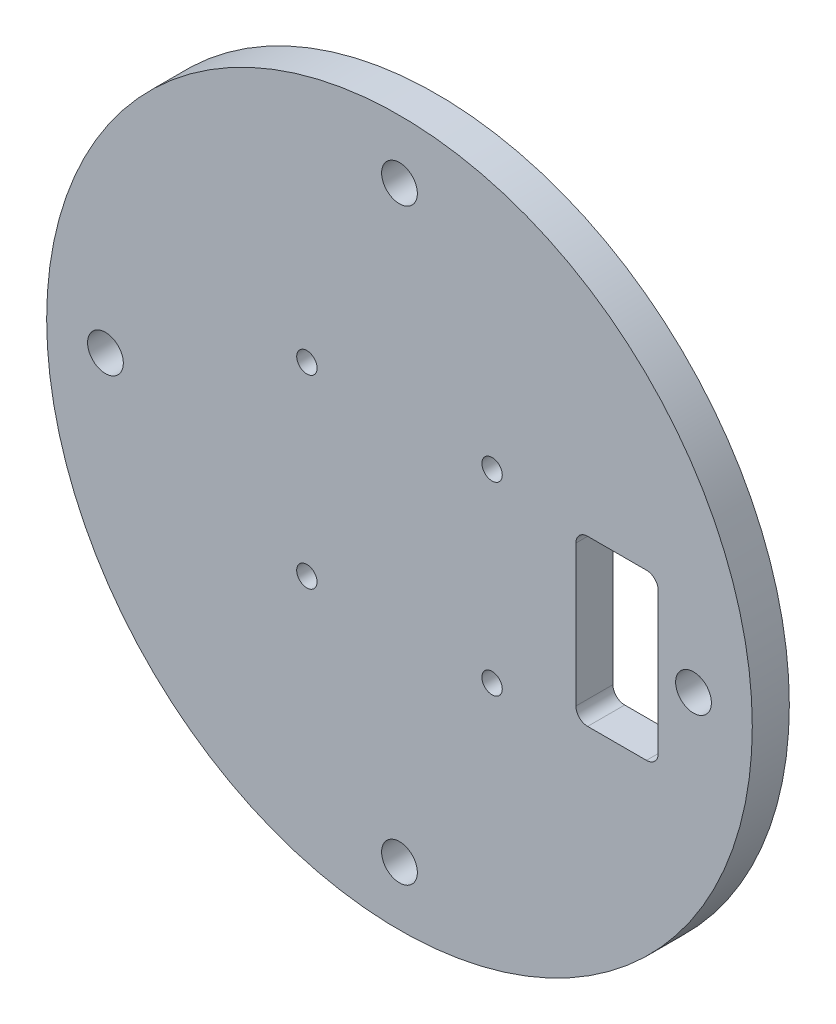
SolidWorks part; units mm, degrees
material "Hexcel AS4C (3000 Filaments)"
ref_plane "Front Plane" through (0, 0, 0) normal (0, 0, 1) x (1, 0, 0)
ref_plane "Top Plane" through (0, 0, 0) normal (0, 1, 0) x (1, 0, 0)
ref_plane "Right Plane" through (0, 0, 0) normal (1, 0, 0) x (0, 0, -1)
sketch "Sketch1" plane through (0, 0, 0) normal (0, 0, 1) x (1, 0, 0)
  circle A0 centre (0, 0) radius 38.1
  dimension "D1" = 76.2
extrude "Boss-Extrude1" add sketch "Sketch1" along normal blind 4 contours A0
sketch "Sketch2" plane through (0, 0, 4) normal (0, 0, 1) x (1, 0, 0)
  circle A0 centre (10, 10) radius 1.1
  circle A1 centre (10, -10) radius 1.1
  circle A2 centre (-10, -10) radius 1.1
  circle A3 centre (-10, 10) radius 1.1
  point P12 (0, 0)
  point P21 (0, 0)
  dimension "D3" = 2.2
  dimension "D1" = 10
  dimension "D2" = 10
  dimension "D4" = 4
extrude "Cut-Extrude1" cut sketch "Sketch2" against normal through all
sketch "Sketch3" plane through (0, 0, 4) normal (0, 0, 1) x (1, 0, 0)
  circle A0 centre (0, -31.75) radius 1.9304
  circle A1 centre (-31.75, 0) radius 1.9304
  circle A2 centre (0, 31.75) radius 1.9304
  circle A3 centre (31.75, 0) radius 1.9304
  point P9 (0, 0)
  dimension "D2" = 3.8608
  dimension "D1" = 31.75
  dimension "D3" = 4
extrude "Cut-Extrude2" cut sketch "Sketch3" against normal through all both and the other way through all
sketch "Sketch4" plane through (0, 0, 4) normal (0, 0, 1) x (1, 0, 0)
  line L1 (20.32, 8.89) -> (26.67, 8.89)
  line L2 (19.05, 7.62) -> (19.05, -7.62)
  line L3 (20.32, -8.89) -> (26.67, -8.89)
  line L4 (27.94, 7.62) -> (27.94, -7.62)
  arc A0 (19.05, -7.62) -> (20.32, -8.89) centre (20.32, -7.62) ccw
  arc A1 (26.67, -8.89) -> (27.94, -7.62) centre (26.67, -7.62) ccw
  arc A2 (26.67, 8.89) -> (27.94, 7.62) centre (26.67, 7.62) cw
  arc A3 (20.32, 8.89) -> (19.05, 7.62) centre (20.32, 7.62) ccw
  point P4 (19.05, 0)
  point P8 (19.05, -8.89)
  point P15 (19.05, 8.89)
  dimension "D4" = 1.27
  dimension "D1" = 8.89
  dimension "D2" = 17.78
  dimension "D3" = 19.05
extrude "Cut-Extrude3" cut sketch "Sketch4" against normal through all both and the other way through all
